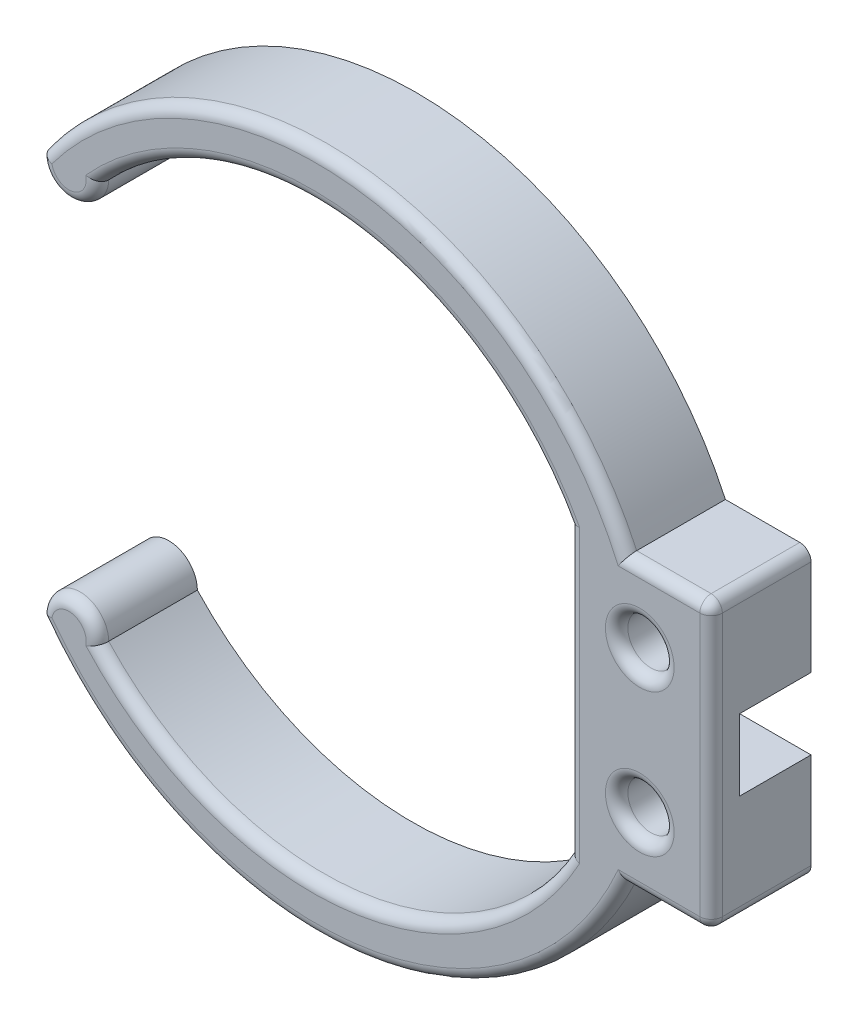
SolidWorks part; units mm, degrees
material "ABS"
ref_plane "Front Plane" through (0, 0, 0) normal (1, 0, 0) x (0, 1, 0)
ref_plane "Top Plane" through (0, 0, 0) normal (0, 0, 1) x (0, 1, 0)
ref_plane "Right Plane" through (0, 0, 0) normal (0, 1, 0) x (-1, 0, 0)
sketch "Sketch2" plane through (0, 0, 0) normal (0, 0, 1) x (0, 1, 0)
  line L0 (0, 0) -> (0, 50000) construction
  line L1 (-12.7, -6.35) -> (12.7, -6.35)
  line L2 (-12.7, -6.35) -> (-12.7, 1.27)
  line L3 (-12.7, 6.35) -> (12.7, 6.35)
  line L4 (12.7, -6.35) -> (12.7, 1.27)
  line L5 (-12.7, -6.35) -> (12.7, 6.35) construction
  line L6 (-12.7, 6.35) -> (12.7, -6.35) construction
  arc A0 (-12.7, 6.35) -> (-17.78, 48.26) centre (0, 29.1523) cw
  arc A1 (-12.7, 1.27) -> (-17.78, 53.34) centre (0, 28.7918) cw
  arc A2 (12.7, 6.35) -> (17.78, 48.26) centre (0, 29.1523) ccw
  arc A3 (12.7, 1.27) -> (17.78, 53.34) centre (0, 28.7918) ccw
  arc A4 (-17.78, 53.34) -> (-17.78, 48.26) centre (-17.78, 50.8) cw
  arc A5 (17.78, 53.34) -> (17.78, 48.26) centre (17.78, 50.8) ccw
  point P0 (0, 0)
  dimension "D5" = 5.08
  dimension "D1" = 25.4
  dimension "D2" = 12.7
  dimension "D3" = 17.78
  dimension "D4" = 41.91
  dimension "D6" = 5.08
  dimension "D7" = 41.91
  dimension "D8" = 35.56
  dimension "D9" = 5.08
  dimension "D10" = 5.08
extrude "Boss-Extrude1" add sketch "Sketch2" along normal blind 8.89
sketch "Sketch3" plane through (0, 0, 8.89) normal (0, 0, 1) x (1, 0, 0)
  line L0 (0, 0) -> (0, 50000) construction
  line L1 (6.35, -12.7) -> (6.35, 12.7) construction
  circle A0 centre (0, -6.35) radius 2.0574
  circle A1 centre (0, 6.35) radius 2.0574
  dimension "D2" = 4.1148
  dimension "D3" = 4.1148
  dimension "D1" = 6.35
  dimension "D4" = 6.35
  dimension "D5" = 12.7
extrude "Cut-Extrude1" cut sketch "Sketch3" against normal blind 8.89
sketch "Sketch4" plane through (6.35, 0, 0) normal (1, 0, 0) x (0, 1, 0)
  line L0 (-12.7, 0) -> (12.7, 0) construction
  line L1 (-3.175, 0) -> (3.175, 0)
  line L2 (-3.175, 0) -> (-3.175, 6.35)
  line L3 (-3.175, 6.35) -> (3.175, 6.35)
  line L4 (3.175, 0) -> (3.175, 6.35)
  dimension "D1" = 6.35
  dimension "D2" = 6.35
  dimension "D3" = 3.175
extrude "Cut-Extrude2" cut sketch "Sketch4" against normal blind 12.7
fillet "Fillet3" radius 1 14 edges at (-50.8, 15.24, 8.89) (-50.8, -15.24, 8.89) (6.35, -12.7, 4.445) (6.35, 12.7, 4.445) (-26.0116, 25.9108, 8.89) (-25.8487, 30.1675, 8.89) (2.54, 12.7, 8.89) (2.54, -12.7, 8.89) (6.35, 0, 8.89) (2.0574, 6.35, 8.89) (2.0574, -6.35, 8.89) (-6.35, 0, 8.89) (-26.0116, -25.9108, 8.89) (-25.8487, -30.1675, 8.89)
